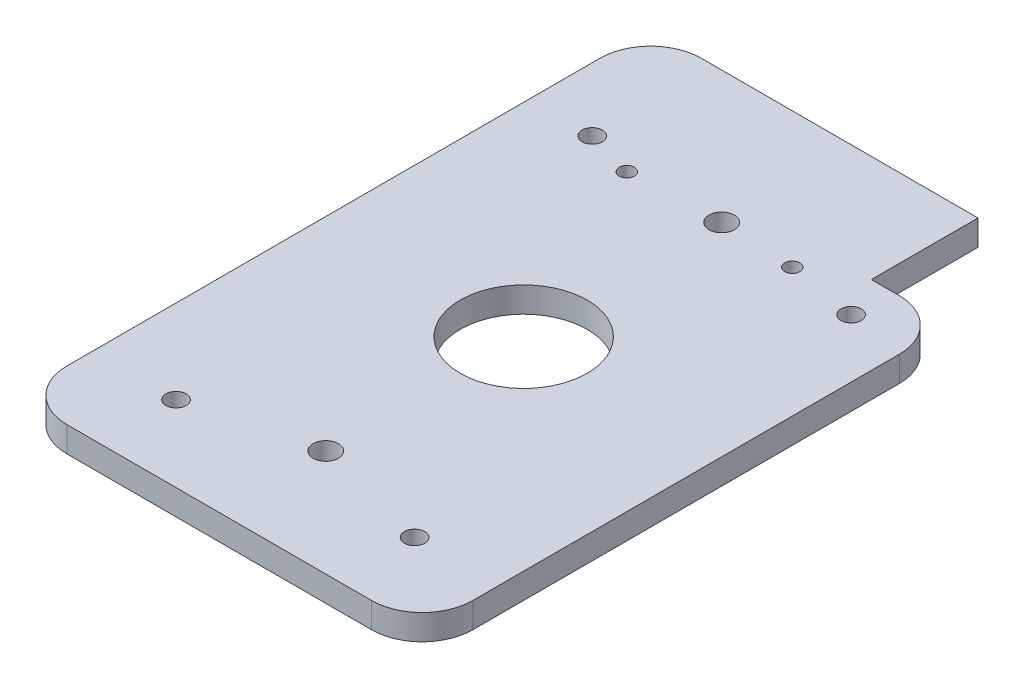
SolidWorks part; units mm, degrees
ref_plane "前视基准面" through (0, 0, 0) normal (0, 0, 1) x (1, 0, 0)
ref_plane "上视基准面" through (0, 0, 0) normal (0, 1, 0) x (1, 0, 0)
ref_plane "右视基准面" through (0, 0, 0) normal (1, 0, 0) x (0, 0, -1)
sketch "草图1" plane through (0, 0, 0) normal (0, 1, 0) x (1, 0, 0)
  line L0 (0, -49.286) -> (0, 59.6782) construction
  line L1 (-40, 65) -> (40, 65)
  line L2 (-40, 65) -> (-40, -60)
  line L3 (-40, -60) -> (40, -60)
  line L4 (40, 65) -> (40, -60)
  circle A0 centre (0, 0) radius 12.5
  dimension "D1" = 60
  dimension "D4" = 25
  dimension "D2" = 80
  dimension "D3" = 125
extrude "凸台-拉伸1" add sketch "草图1" along normal blind 5
sketch "草图2" plane through (0, 5, 0) normal (0, 1, 0) x (1, 0, 0)
  line L0 (40, 65) -> (-40, 65) construction
  line L1 (24.5, 65) -> (40, 65)
  line L2 (24.5, 65) -> (24.5, 44)
  line L3 (24.5, 44) -> (40, 44)
  line L4 (40, 65) -> (40, 44)
  line L5 (40, -60) -> (40, 65) construction
  dimension "D1" = 15.5
  dimension "D2" = 21
extrude "切除-拉伸1" cut sketch "草图2" against normal through all
hole_wizard "大小mm Clearance 暗销孔1" positions "草图3" profile "草图4" hole size "Ø4.0" standard "GB" end condition through all
sketch "草图3" plane through (0, 5, 0) normal (0, 1, 0) x (1, 0, 0)
  line L0 (0, -59.3844) -> (0, 58.2895) construction
  line L2 (30.3997, 0) -> (-33.5358, 0) construction
  point P0 (-23.5, -45)
  point P3 (23.5, -45)
  point P6 (28.5, 36)
  point P9 (-27.5, 41)
  dimension "D1" = 45
  dimension "D2" = 23.5
  dimension "D3" = 41
  dimension "D4" = 27.5
  dimension "D5" = 28.5
  dimension "D6" = 36
sketch "草图4" plane through (-23.5, 5, 45) normal (1, 0, 0) x (0, 0, 1)
  line L0 (0, 0) -> (0, 5)
  line L1 (0, 5) -> (2, 5)
  line L2 (2, 5) -> (2, 0)
  line L5 (2, 0) -> (0, 0)
  line L11 (0, -6.35) -> (0, 107.95) construction
  dimension "通孔孔直径" = 4
  dimension "通孔孔深度" = 5
hole_wizard "大小mm Transitional 暗销孔1" positions "草图5" profile "草图6" hole size "Ø5.0" standard "GB" end condition through all
sketch "草图5" plane through (0, 5, 0) normal (0, 1, 0) x (1, 0, 0)
  line L0 (28.4574, 0) -> (-29.0037, 0) construction
  line L1 (28.4574, 0) -> (-30.1367, 0) construction
  point P0 (0, -39)
  point P3 (0, 39)
  dimension "D1" = 39
sketch "草图6" plane through (0, 5, 39) normal (1, 0, 0) x (0, 0, 1)
  line L0 (0, 0) -> (0, 5)
  line L1 (0, 5) -> (2.5, 5)
  line L2 (2.5, 5) -> (2.5, 0)
  line L5 (2.5, 0) -> (0, 0)
  line L11 (0, -6.35) -> (0, 107.95) construction
  dimension "通孔孔直径" = 5
  dimension "通孔孔深度" = 5
fillet "圆角1" radius 10 4 edges at (40, 2.5, 60) (-40, 2.5, 60) (-40, 2.5, -65) (40, 2.5, -44)
hole_wizard "大小mm Transitional 暗销孔2" positions "草图9" profile "草图10" hole size "Ø3.0" standard "GB" end condition through all
sketch "草图9" plane through (0, 5, 0) normal (0, 1, 0) x (1, 0, 0)
  line L0 (0, 0) -> (0, 52.6631) construction
  line L2 (22.6815, 0) -> (-25.0677, 0) construction
  point P0 (14.6094, 38.3)
  point P3 (-18, 38.3)
  dimension "D1" = 14.6094
  dimension "D2" = 18
  dimension "D3" = 38.3
  dimension "D4" = 38.3
sketch "草图10" plane through (14.6094, 5, -38.3) normal (1, 0, 0) x (0, 0, 1)
  line L0 (0, 0) -> (0, 5)
  line L1 (0, 5) -> (1.5, 5)
  line L2 (1.5, 5) -> (1.5, 0)
  line L5 (1.5, 0) -> (0, 0)
  line L11 (0, -6.35) -> (0, 107.95) construction
  dimension "通孔孔直径" = 3
  dimension "通孔孔深度" = 5
